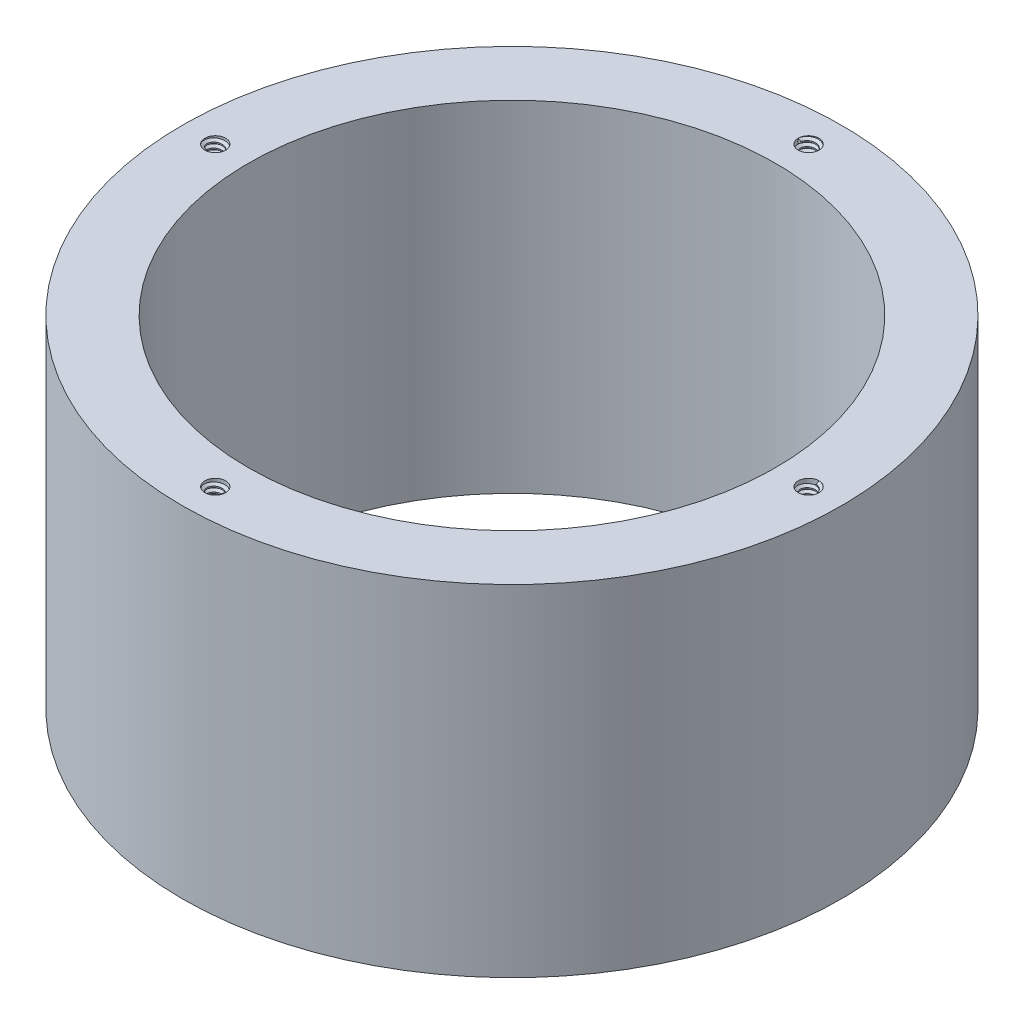
SolidWorks part; units mm, degrees
material "1060 Alloy"
ref_plane "Front Plane" through (0, 0, 0) normal (0, 0, 1) x (1, 0, 0)
ref_plane "Top Plane" through (0, 0, 0) normal (0, 1, 0) x (1, 0, 0)
ref_plane "Right Plane" through (0, 0, 0) normal (1, 0, 0) x (0, 0, -1)
sketch "Sketch1" plane through (0, 0, 0) normal (0, 1, 0) x (1, 0, 0)
  circle A0 centre (0, 0) radius 12.7
  circle A1 centre (0, 0) radius 15.875
  dimension "D1" = 25.4
  dimension "D2" = 31.75
extrude "Boss-Extrude1" add sketch "Sketch1" along normal blind 16.4
sketch "Sketch2" plane through (0, 16.4, 0) normal (0, 1, 0) x (1, 0, 0)
  circle A0 centre (0, 14.29) radius 0.5
  dimension "D1" = 1
  dimension "D2" = 14.29
extrude "Cut-Extrude1" cut sketch "Sketch2" against normal blind 2
thread "Thread1" pitch 0.25 method extrude profile "Thread Profile2" start angle 0, offset 0, length 2, pitch 0.25, diameter 1
ref_plane "Plane2" through (-0.5, 16.4, -14.29) normal (0, 0, 1) x (-1, 0, 0)
sketch "Thread Profile2" plane through (-0.5, 16.4, -14.29) normal (0, 0, 1) x (-1, 0, 0)
  line L0 (0, 0) -> (0, 0.25) construction
  line L11 (0, 0) -> (0, 0.2187)
  line L12 (0, 0.2187) -> (-0.1353, 0.1406)
  line L13 (-0.1353, 0.1406) -> (-0.1353, 0.0781)
  line L15 (-0.1353, 0.0781) -> (0, 0)
  line L17 (-0.1353, 0.1094) -> (0, 0.1094) construction
  point P2 (0, 0)
  dimension "Pitch" = 0.25
  dimension "Profile_Angle" = 60
  dimension "Profile_Land" = 0.0625
  dimension "Profile_Height" = 0.1353
pattern_circular "CirPattern1" count 4 over 360 about axis through (0, 16.4, 0) along (0, 1, 0) of "Cut-Extrude1", "Thread1"
sketch "Sketch7" plane through (0, 0, 0) normal (0, -1, 0) x (1, 0, 0)
  circle A0 centre (0, 14.29) radius 0.5
  dimension "D1" = 1
  dimension "D2" = 14.29
extrude "Cut-Extrude2" cut sketch "Sketch7" against normal blind 2
thread "Thread2" pitch 0.25 method extrude profile "Thread Profile3" start angle 0, offset 0, length 2, pitch 0.25, diameter 1
ref_plane "Plane3" through (0.5, 0, 14.29) normal (0, 0, 1) x (1, 0, 0)
sketch "Thread Profile3" plane through (0.5, 0, 14.29) normal (0, 0, 1) x (1, 0, 0)
  line L0 (0, 0) -> (0, 0.25) construction
  line L11 (0, 0) -> (0, 0.2187)
  line L12 (0, 0.2187) -> (-0.1353, 0.1406)
  line L13 (-0.1353, 0.1406) -> (-0.1353, 0.0781)
  line L15 (-0.1353, 0.0781) -> (0, 0)
  line L17 (-0.1353, 0.1094) -> (0, 0.1094) construction
  point P2 (0, 0)
  dimension "Pitch" = 0.25
  dimension "Profile_Angle" = 60
  dimension "Profile_Land" = 0.0625
  dimension "Profile_Height" = 0.1353
pattern_circular "CirPattern2" count 4 over 360 about axis through (0, 0, 0) along (0, 1, 0) of "Thread2", "Cut-Extrude2"
